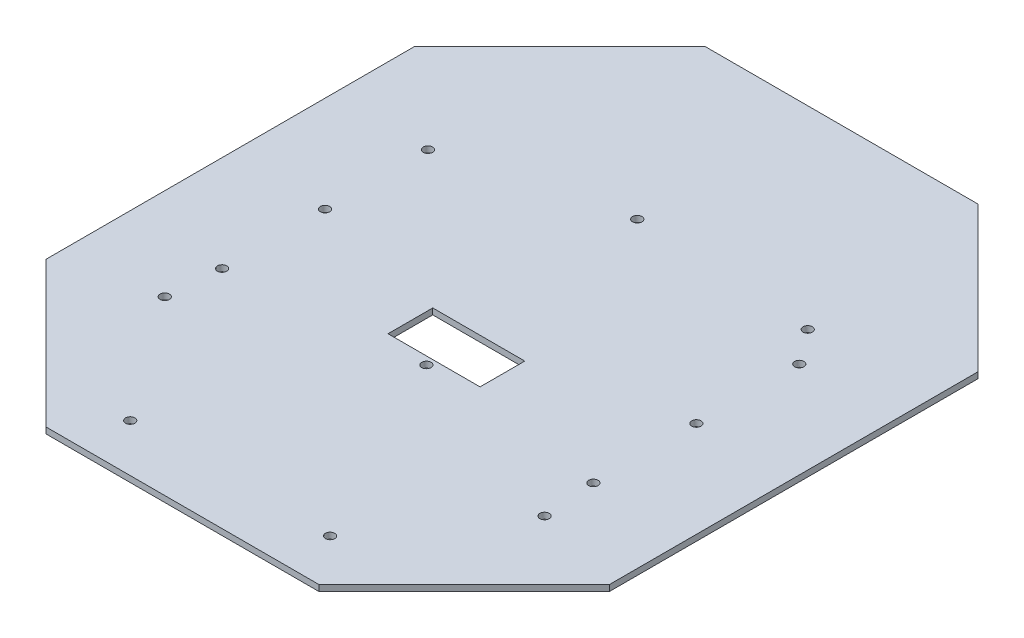
SolidWorks part; units mm, degrees
ref_plane "Front Plane" through (0, 0, 0) normal (0, 0, 1) x (1, 0, 0)
ref_plane "Top Plane" through (0, 0, 0) normal (0, 1, 0) x (1, 0, 0)
ref_plane "Right Plane" through (0, 0, 0) normal (1, 0, 0) x (0, 0, -1)
sketch "Sketch14" plane through (0, 0, 0) normal (0, 1, 0) x (1, 0, 0)
  line L1 (224, 92.7838) -> (92.7838, 224)
  line L2 (92.7838, 224) -> (-92.7838, 224)
  line L3 (-92.7838, 224) -> (-224, 92.7838)
  line L4 (-224, 92.7838) -> (-224, -92.7838)
  line L5 (-224, -92.7838) -> (-92.7838, -224)
  line L6 (-92.7838, -224) -> (92.7838, -224)
  line L7 (92.7838, -224) -> (224, -92.7838)
  line L8 (224, -92.7838) -> (224, 92.7838)
  circle A0 centre (0, 0) radius 224 construction
extrude "Boss-Extrude2" add sketch "Sketch14" along normal blind 4.12
sketch "Sketch16" plane through (0, 0, 0) normal (0, -1, 0) x (1, 0, 0)
  line L0 (-191.5, -224) -> (-191.5, 224)
  line L1 (-191.5, -224) -> (191.5, -224)
  line L2 (-191.5, 224) -> (191.5, 224)
  line L3 (191.5, -224) -> (191.5, 224)
  line L4 (-191.5, -224) -> (191.5, 224) construction
  line L5 (-191.5, 224) -> (191.5, -224) construction
  point P1 (0, 0)
  dimension "D1" = 383
ref_point "Point9"
ref_point "Point10"
sketch "Sketch17" plane through (0, 0, 0) normal (0, -1, 0) x (1, 0, 0)
  line L0 (191.5, 125.2838) -> (191.5, -125.742)
  line L1 (191.5, -125.742) -> (224, -92.7838)
  line L2 (224, -92.7838) -> (224, 92.7838)
  line L3 (224, 92.7838) -> (191.5, 125.2838)
extrude "Cut-Extrude2" cut sketch "Sketch17" against normal blind 4.12
ref_point "Point11"
ref_point "Point12"
sketch "Sketch18" plane through (0, 0, 0) normal (0, -1, 0) x (1, 0, 0)
  line L0 (-191.5, 125.2838) -> (-224, 92.7838)
  line L1 (-224, 92.7838) -> (-224, -92.7838)
  line L2 (-224, -92.7838) -> (-191.5, -125.2838)
  line L3 (-191.5, -125.2838) -> (-191.5, 125.2838)
extrude "Cut-Extrude3" cut sketch "Sketch18" against normal blind 4.12
hole_wizard "1/4 (0.25) Diameter Hole1" positions "Sketch19" profile "Sketch21" hole size "1/4" standard "ANSI Inch" end condition up to next
sketch "Sketch19" plane through (0, 4.12, 0) normal (0, 1, 0) x (1, 0, 0)
  point P2 (67.9635, -191.609)
  point P5 (-67.9265, -191.609)
  point P8 (-129.0643, -106.9889)
  point P11 (-126.1941, -70.8955)
  point P14 (-126.1941, -0.9185)
  point P17 (-126.1941, 69.0585)
  point P20 (-14.1039, 99.2591)
  point P23 (108.7305, 92.2995)
  point P26 (126.2311, 69.0585)
  point P29 (126.2311, -0.9185)
  point P32 (129.1013, -106.9889)
  point P35 (126.2311, -70.8955)
  point P38 (0.0185, -58.1955)
sketch "Sketch21" plane through (67.9635, 4.12, 191.609) normal (1, 0, 0) x (0, 0, 1)
  line L0 (0, 0) -> (0, 4.12)
  line L1 (0, 4.12) -> (3.175, 4.12)
  line L2 (3.175, 4.12) -> (3.175, 0)
  line L5 (3.175, 0) -> (0, 0)
  line L11 (0, -6.35) -> (0, 107.95) construction
  dimension "Thru Hole Dia." = 6.35
  dimension "Thru Hole Depth" = 4.12
sketch "Sketch22" plane through (0, 4.12, 0) normal (0, 1, 0) x (1, 0, 0)
  line L1 (31.1658, -52.8764) -> (-31.3997, -52.8764)
  line L2 (31.1658, -52.8764) -> (31.1658, -22.4822)
  line L3 (31.1658, -22.4822) -> (-31.3997, -22.4822)
  line L4 (-31.3997, -52.8764) -> (-31.3997, -22.4822)
extrude "Cut-Extrude4" cut sketch "Sketch22" against normal up to next
sketch "Sketch23" plane through (0, 0, 224) normal (0, 0, 1) x (1, 0, 0)
  line L0 (0, 4.12) -> (0, 0)
  line L1 (-92.7838, 4.12) -> (92.7838, 4.12) construction
  line L2 (-92.7838, 0) -> (92.7838, 0) construction
